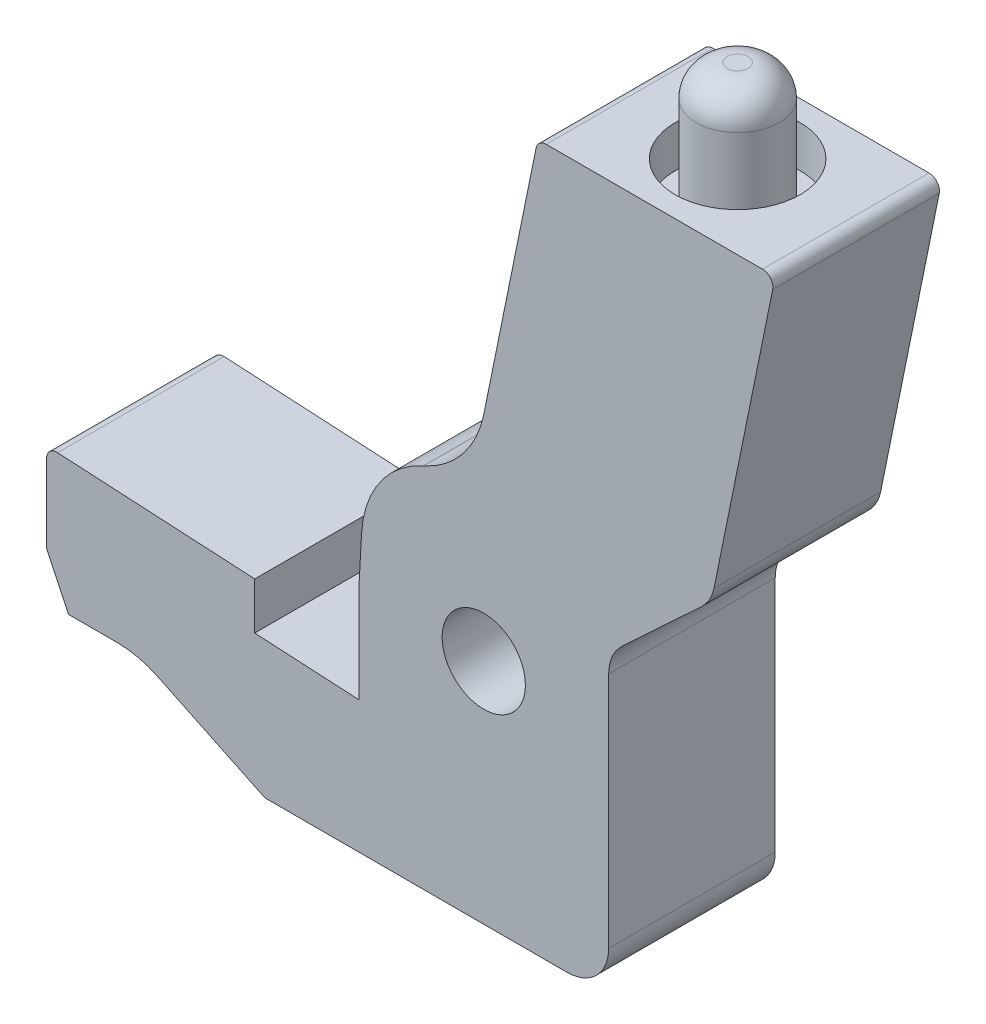
SolidWorks part; units mm, degrees
ref_plane "정면" through (0, 0, 0) normal (0, 0, 1) x (1, 0, 0)
ref_plane "윗면" through (0, 0, 0) normal (0, 1, 0) x (1, 0, 0)
ref_plane "우측면" through (0, 0, 0) normal (1, 0, 0) x (0, 0, -1)
sketch "스케치1" plane through (0, 0, 0) normal (0, 0, 1) x (1, 0, 0)
  line L0 (6, 0) -> (6, 2.4715)
  line L1 (-2.9092, 6.6721) -> (-2.8684, 6.6903)
  line L2 (0, 10.2614) -> (2.5126, 22.5998)
  line L3 (3.0026, 23) -> (13.3879, 23)
  line L4 (13.8779, 22.4002) -> (11.0612, 8.5688)
  line L5 (10.4654, 7.5052) -> (6.636, 3.9342)
  line L6 (-5.8708, 2.3748) -> (-6, 0)
  line L7 (-6, 0) -> (-6, -4.6014)
  line L8 (-6, -4.6014) -> (-11, -4.3293)
  line L9 (-11, -4.3293) -> (-11, -2.0785)
  line L10 (-11, -2.0785) -> (-20.4728, -1.5631)
  line L11 (-21, -2.0623) -> (-21, -5.7956)
  line L12 (-21, -5.7956) -> (-19.9469, -8.0272)
  line L13 (-19.9469, -8.0272) -> (-17.6181, -8.0272)
  line L14 (-15.664, -8.4715) -> (-10.5112, -10.9422)
  line L15 (-10.5112, -10.9422) -> (4, -10.9422)
  line L16 (6, -8.9422) -> (6, 0)
  circle A0 centre (0, 0) radius 2
  arc A1 (-5.9646, 0.6509) -> (-6, 0) centre (0, 0) ccw
  arc A2 (-5.9646, 0.6509) -> (-6, 0) centre (0, 0) ccw
  arc A3 (-5.8708, 2.3748) -> (-2.9092, 6.6721) centre (-0.8782, 2.1032) cw
  arc A4 (-2.8684, 6.6903) -> (0, 10.2614) centre (-4.8994, 11.2592) ccw
  arc A5 (6, 2.4715) -> (6.636, 3.9342) centre (8, 2.4715) cw
  arc A6 (11.0612, 8.5688) -> (10.4654, 7.5052) centre (9.1014, 8.9679) cw
  arc A7 (-20.4728, -1.5631) -> (-21, -2.0623) centre (-20.5, -2.0623) ccw
  arc A8 (4, -10.9422) -> (6, -8.9422) centre (4, -8.9422) ccw
  arc A9 (2.5126, 22.5998) -> (3.0026, 23) centre (3.0026, 22.5) cw
  arc A10 (13.3879, 23) -> (13.8779, 22.4002) centre (13.3879, 22.5) cw
  arc A11 (-17.6181, -8.0272) -> (-15.664, -8.4715) centre (-17.6181, -12.5468) cw
  point P32 (-21, -1.5344)
  point P37 (2.5941, 23)
  point P40 (14, 23)
  dimension "D1" = 4
  dimension "D2" = 23
  dimension "D3" = 14
  dimension "D4" = 133
  dimension "D5" = 5
  dimension "D6" = 21
  dimension "D7" = 2
  dimension "D8" = 5
  dimension "D9" = 2
  dimension "D10" = 0.5
  dimension "D11" = 4.5196
sketch "스케치2" plane through (0, 0, 0) normal (0, 0, 1) x (1, 0, 0)
extrude "보스-돌출1" add sketch "스케치1" along normal blind 8 contours L13 A11 L14 L15 A8 L16 L0 A5 L5 A6 L4 A10 L3 A9 L2 A4 L1 A3 L6 L7 L8 L9 L10 A7 L11 L12 A0 region at (-0.1255, 3.5353, 0)
sketch "스케치4" plane through (0, 23, 0) normal (0, 1, 0) x (1, 0, 0)
  line L0 (3.0026, 0) -> (13.3879, -8) construction
  circle A0 centre (8.1952, -4) radius 3
  circle A1 centre (8.1952, -4) radius 2
  dimension "D1" = 6
  dimension "D2" = 4
extrude "컷-돌출1" cut sketch "스케치4" against normal blind 2 contours L0 A0 A1 | A0 L0 A1 region at (9.1389, 23, 1.2285) region at (6.1706, 23, 2.5316)
extrude "보스-돌출2" add sketch "스케치4<3>" along normal blind 4 contours A1
sketch "스케치4<3>" plane through (0, 23, 0) normal (0, 1, 0) x (1, 0, 0) same geometry as "스케치4"
fillet "필렛1" radius 1.5 1 edges at (8.1952, 27, 6)
